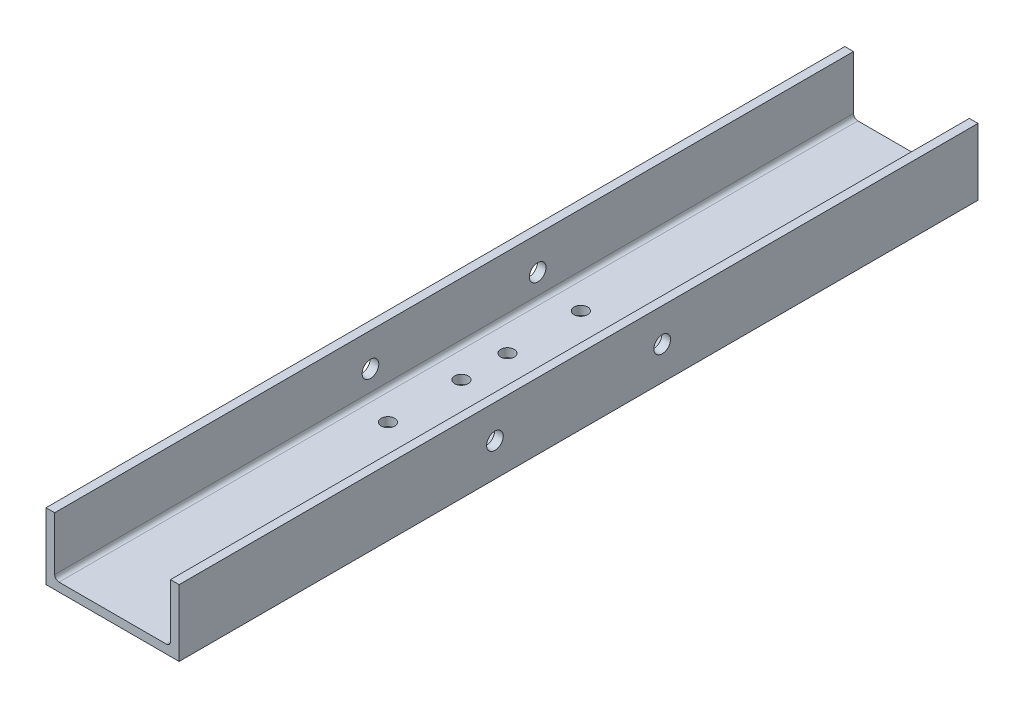
SolidWorks part; units mm, degrees
ref_plane "Front Plane" through (0, 0, 0) normal (0, 0, 1) x (1, 0, 0)
ref_plane "Top Plane" through (0, 0, 0) normal (0, 1, 0) x (1, 0, 0)
ref_plane "Right Plane" through (0, 0, 0) normal (1, 0, 0) x (0, 0, -1)
sketch "Sketch1" plane through (0, 0, 0) normal (0, 0, 1) x (1, 0, 0)
  line L0 (-25.4, 12.7) -> (-25.4, -12.7) construction
  line L1 (-25.4, -12.7) -> (25.4, -12.7) construction
  line L2 (25.4, -12.7) -> (25.4, 12.7) construction
  line L3 (22.098, -9.398) -> (-22.098, -9.398) construction
  line L4 (-22.098, -9.398) -> (-22.098, 12.7) construction
  line L6 (-22.098, 12.7) -> (-25.4, 12.7) construction
  line L7 (0, -12.7) -> (0, 0) construction
  line L8 (25.4, 12.7) -> (22.098, 12.7) construction
  line L9 (22.098, 12.7) -> (22.098, -9.398) construction
  line L10 (0, -9.398) -> (0, -12.7) construction
  point P4 (0, 0)
  point P11 (25.4, -9.398)
  dimension "Outside Height" = 25.4
  dimension "Outside Width" = 50.8
  dimension "Leg Thickness" = 3.302
  dimension "D1" = 12.7
  dimension "Inside Height" = 22.098
  dimension "Inside Width" = 44.196
  dimension "Base Thickness" = 3.302
sketch "Sketch2" plane through (0, 0, 0) normal (1, 0, 0) x (0, 0, -1)
  line L0 (210.695, 12.7) -> (-210.695, 12.7) construction
  line L1 (0, -9.398) -> (0, 12.7) construction
  point P0 (-159.895, 12.7)
  point P4 (0, 12.7)
  point P6 (159.895, 12.7)
  dimension "D1" = 50.8
  dimension "D2" = 50.8
  dimension "Length" = 421.39
sketch "Sketch3" plane through (0, 0, 0) normal (0, 0, 1) x (1, 0, 0)
  line L6 (-25.4, 12.7) -> (-25.4, -12.7)
  line L7 (-25.4, -12.7) -> (25.4, -12.7)
  line L8 (25.4, -12.7) -> (25.4, 12.7)
  line L9 (25.4, 12.7) -> (22.098, 12.7)
  line L10 (22.098, 12.7) -> (22.098, -9.398)
  line L11 (22.098, -9.398) -> (-22.098, -9.398)
  line L12 (-22.098, -9.398) -> (-22.098, 12.7)
  line L13 (-22.098, 12.7) -> (-25.4, 12.7)
extrude "Boss-Extrude1" add sketch "Sketch3" along normal mid plane 304.8
fillet "Fillet1" radius 1.651 2 edges at (22.098, -9.398, 0) (-22.098, -9.398, 0)
sketch "Sketch4" plane through (0, -9.398, 0) normal (0, 1, 0) x (1, 0, 0)
  line L0 (0, 152.4) -> (0, -152.4) construction
  line L1 (20.447, 152.4) -> (-20.447, 152.4) construction
  line L2 (20.447, -152.4) -> (-20.447, -152.4) construction
  line L3 (-23.5304, 0) -> (23.5304, 0) construction
  circle A0 centre (-10.5304, 8.79) radius 2.585
  circle A1 centre (10.4696, 8.79) radius 2.585
  circle A2 centre (-10.5304, 36.79) radius 2.585
  circle A3 centre (10.4696, 36.79) radius 2.585
  circle A4 centre (-10.5304, -36.79) radius 2.585
  circle A5 centre (10.4696, -36.79) radius 2.585
  circle A6 centre (10.4696, -8.79) radius 2.585
  circle A7 centre (-10.5304, -8.79) radius 2.585
  point P24 (0, 0)
  point P26 (0, 0)
  dimension "D1" = 5.17
  dimension "D2" = 5.17
  dimension "D3" = 28
  dimension "D4" = 8.79
  dimension "D5" = 8.79
  dimension "D6" = 28
extrude "Cut-Extrude1" cut sketch "Sketch4" against normal blind 10
sketch "Sketch9" plane through (0, 0, 0) normal (1, 0, 0) x (0, 0, -1)
  line L0 (0, 0) -> (0, -12.7) construction
  line L1 (-152.4, -12.7) -> (152.4, -12.7) construction
  line L2 (0, 0) -> (-95.1707, 0) construction
  circle A0 centre (-31.91, 0) radius 3.18
  circle A1 centre (31.91, 0) radius 3.18
  dimension "D2" = 6.36
  dimension "D1" = 31.91
extrude "Cut-Extrude2" cut sketch "Sketch9" against normal mid plane 60
equation "\"D1@Boss-Extrude1\"=\"Length@Sketch2\""
equation "\"D2@Sketch2\"=\"D1@Sketch2\""
equation "\"D1@Sketch1\"=\"Outside Height@Sketch1\"/2"
equation "\"D1@Fillet1\"=\"Leg Thickness@Sketch1\"*.5"
equation "\"D1@Sketch2\"=\"Outside Width@Sketch1\"*1"
